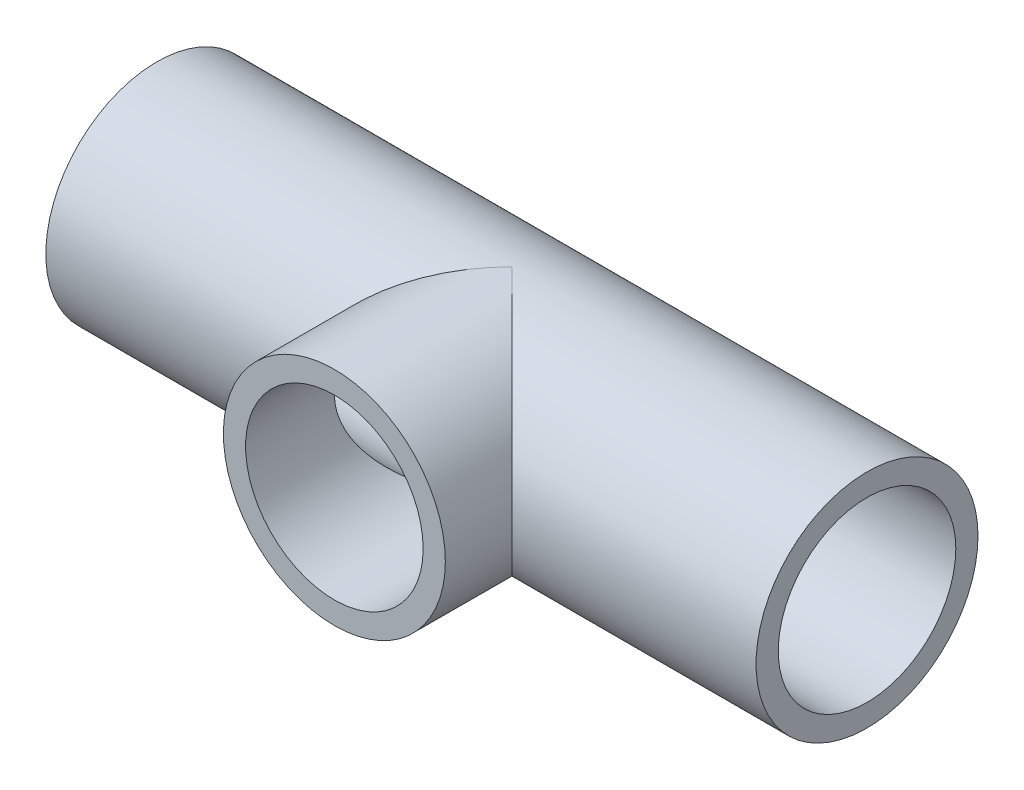
SolidWorks part; units mm, degrees
material "PVC Rigid"
ref_plane "Front Plane" through (0, 0, 0) normal (0, 0, 1) x (1, 0, 0)
ref_plane "Top Plane" through (0, 0, 0) normal (0, 1, 0) x (1, 0, 0)
ref_plane "Right Plane" through (0, 0, 0) normal (1, 0, 0) x (0, 0, -1)
sketch "Sketch4" plane through (0, 0, 0) normal (0, 0, 1) x (1, 0, 0)
  circle A0 centre (0, 0) radius 7.9375
  dimension "D1" = 15.875
extrude "Boss-Extrude2" add sketch "Sketch4" along normal blind 12.7
ref_axis "Axis1" through (0, 0, 12.7) along (0, 0, -1)
sketch "Sketch7" plane through (0, 0, 12.7) normal (0, 0, 1) x (1, 0, 0)
  circle A0 centre (0, 0) radius 6.35
  dimension "D1" = 12.7
extrude "Cut-Extrude2" cut sketch "Sketch7" against normal blind 12.7
sketch "Sketch8" plane through (0, 0, 0) normal (1, 0, 0) x (0, 0, -1)
  circle A0 centre (0, 0) radius 7.9375
  dimension "D1" = 15.875
extrude "Boss-Extrude4" add sketch "Sketch8" along normal mid plane 50.8
sketch "Sketch9" plane through (25.4, 0, 0) normal (1, 0, 0) x (0, 0, -1)
  circle A0 centre (0, 0) radius 6.35
  dimension "D1" = 12.7
sketch "Sketch10" plane through (0, 0, 12.7) normal (0, 0, 1) x (1, 0, 0)
  circle A0 centre (0, 0) radius 6.35
  dimension "D1" = 12.7
extrude "Cut-Extrude4" cut sketch "Sketch10" against normal blind 12.7
extrude "Cut-Extrude5" cut sketch "Sketch9" against normal through all
